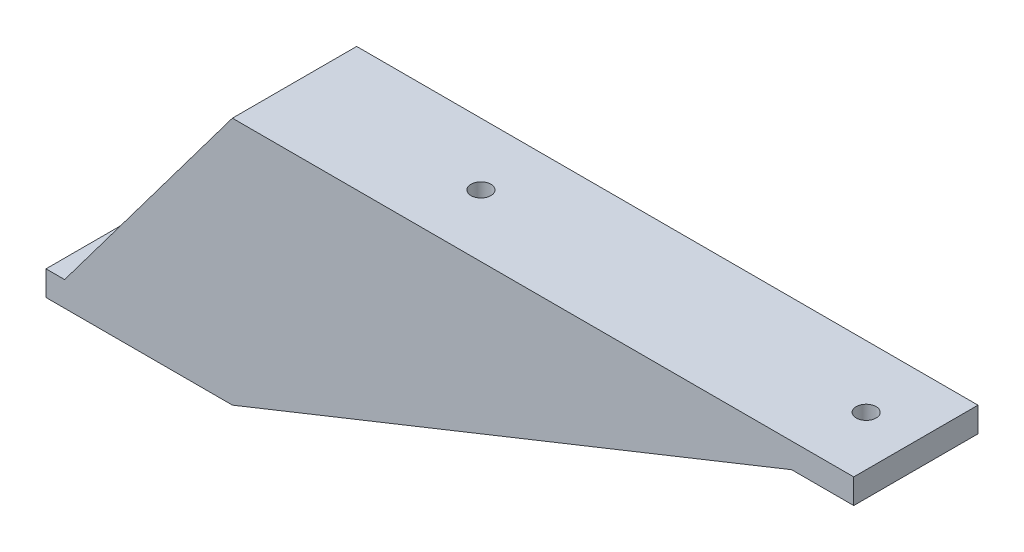
SolidWorks part; units mm, degrees
ref_plane "Front Plane" through (0, 0, 0) normal (0, 0, 1) x (1, 0, 0)
ref_plane "Top Plane" through (0, 0, 0) normal (0, 1, 0) x (1, 0, 0)
ref_plane "Right Plane" through (0, 0, 0) normal (1, 0, 0) x (0, 0, -1)
sketch "Sketch1" plane through (0, 0, 0) normal (0, 0, 1) x (1, 0, 0)
  line L0 (0, 0) -> (-15, 0)
  line L1 (0, 20) -> (50, 20)
  line L2 (50, 20) -> (0, 0)
  line L3 (-15, 0) -> (0, 20)
extrude "Boss-Extrude1" add sketch "Sketch1" along normal blind 2
sketch "Sketch2" plane through (0, 20, 0) normal (0, 1, 0) x (1, 0, 0)
  line L1 (50, -2) -> (0, -2)
  line L2 (50, -2) -> (50, 8)
  line L3 (50, 8) -> (0, 8)
  line L4 (0, -2) -> (0, 8)
extrude "Boss-Extrude2" add sketch "Sketch2" against normal blind 2
sketch "Sketch3" plane through (0, 0, 0) normal (0, -1, 0) x (1, 0, 0)
  line L1 (-15, 2) -> (0, 2)
  line L2 (-15, 2) -> (-15, -8)
  line L3 (-15, -8) -> (0, -8)
  line L4 (0, 2) -> (0, -8)
extrude "Boss-Extrude3" add sketch "Sketch3" against normal blind 2
sketch "Sketch4" plane through (0, 0, -8) normal (0, 0, -1) x (-1, 0, 0)
  line L0 (-50, 20) -> (0, 0)
  line L1 (0, 0) -> (15, 0)
  line L2 (15, 0) -> (0, 0) construction
  line L3 (15, 0) -> (0, 20)
  line L4 (-50, 20) -> (0, 20) construction
  line L5 (0, 20) -> (13.5, 2) construction
  line L6 (0, 20) -> (-50, 20)
extrude "Boss-Extrude4" add sketch "Sketch4" against normal blind 2
sketch "Sketch6" plane through (0, 0, 0) normal (0, 0, -1) x (-1, 0, 0)
  line L0 (0, 20) -> (0, 18)
  line L1 (0, 18) -> (-1, 18)
  line L2 (0, 18) -> (-45, 18) construction
  line L3 (-1, 18) -> (-1, 0.4)
  line L4 (0, 0) -> (-45, 18) construction
  line L5 (-1, 0.4) -> (0, 0)
  line L6 (0, 0) -> (0, 2)
  line L7 (0, 2) -> (1, 2)
  line L8 (0, 2) -> (13.5, 2) construction
  line L9 (1, 2) -> (1, 18.6667)
  line L10 (0, 20) -> (13.5, 2) construction
  line L11 (1, 18.6667) -> (0, 20)
extrude "Boss-Extrude5" add sketch "Sketch6" along normal blind 6
sketch "Sketch7" plane through (0, 20, 0) normal (0, 1, 0) x (1, 0, 0)
  line L0 (50, -2) -> (50, 8) construction
  line L1 (-15, -2) -> (-15, 8) construction
  circle A0 centre (46, 3) radius 0.8
  circle A1 centre (15, 3) radius 0.8
  circle A2 centre (-11, 3) radius 0.8
  circle A3 centre (-5, 3) radius 0.8
  dimension "D1" = 4
  dimension "D3" = 4
  dimension "D4" = 6
  dimension "D2" = 35
extrude "Cut-Extrude1" cut sketch "Sketch7" against normal blind 20
ref_axis "Axis1" through (46, 18, -3) along (0, 1, 0)
ref_axis "Axis2" through (15, 18, -3) along (0, 1, 0)
ref_axis "Axis3" through (-5, 0, -3) along (0, 1, 0)
ref_axis "Axis4" through (-11, 0, -3) along (0, 1, 0)
